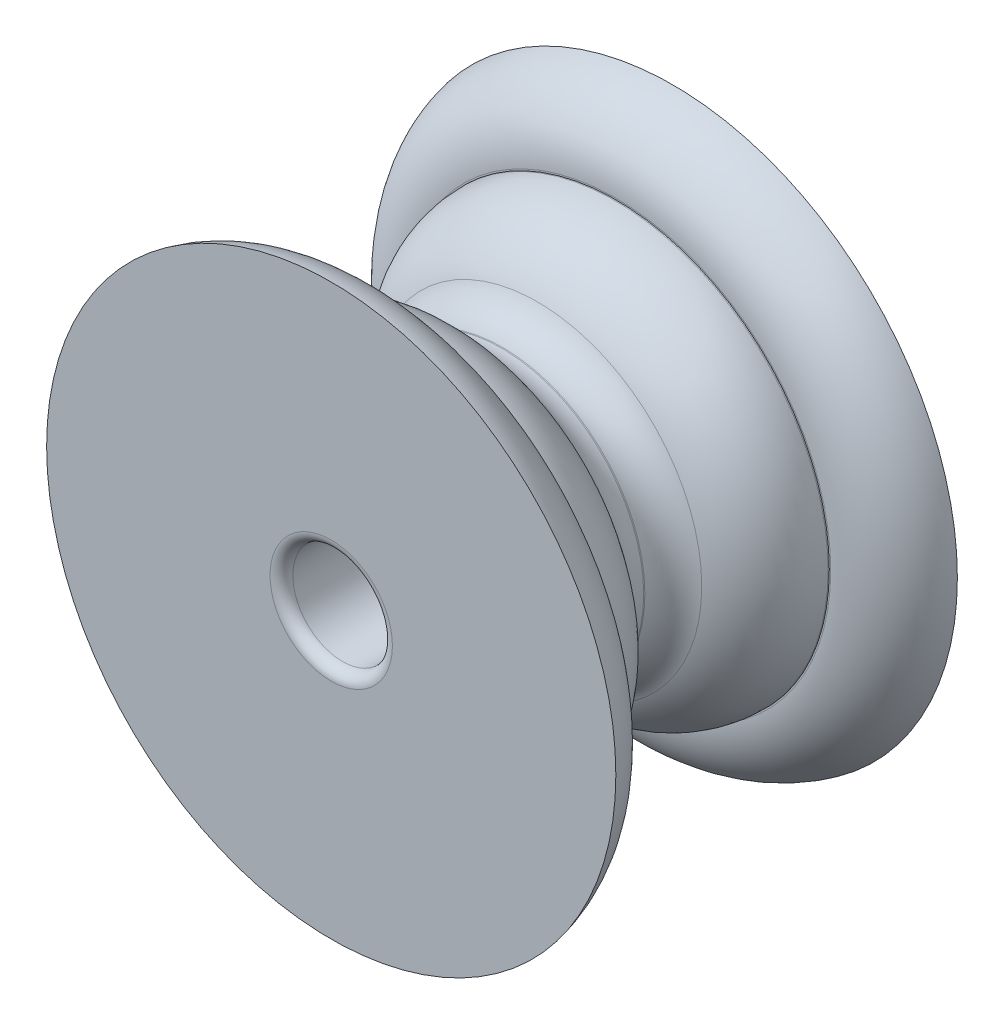
SolidWorks part; units mm, degrees
ref_plane "前视基准面" through (0, 0, 0) normal (0, 0, 1) x (1, 0, 0)
ref_plane "上视基准面" through (0, 0, 0) normal (0, 1, 0) x (1, 0, 0)
ref_plane "右视基准面" through (0, 0, 0) normal (1, 0, 0) x (0, 0, -1)
other "Configuration Table"
sketch "草图1" plane through (0, 0, 0) normal (0, 0, 1) x (1, 0, 0)
  circle A0 centre (0, 0) radius 10
  dimension "D1" = 20
extrude "凸台-拉伸1" add sketch "草图1" along normal blind 2
sketch "草图2" plane through (0, 0, 2) normal (0, 0, 1) x (1, 0, 0)
  circle A0 centre (0, 0) radius 7.5
  dimension "D1" = 15
extrude "凸台-拉伸2" add sketch "草图2" along normal blind 3
sketch "草图3" plane through (0, 0, 5) normal (0, 0, 1) x (1, 0, 0)
  circle A0 centre (0, 0) radius 5
  dimension "D1" = 10
extrude "凸台-拉伸3" add sketch "草图3" along normal blind 2
sketch "草图4" plane through (0, 0, 7) normal (0, 0, 1) x (1, 0, 0)
  circle A0 centre (0, 0) radius 7.5 construction
  circle A1 centre (0, 0) radius 7.5
extrude "凸台-拉伸4" add sketch "草图4" along normal blind 3
sketch "草图5" plane through (0, 0, 10) normal (0, 0, 1) x (1, 0, 0)
  circle A0 centre (0, 0) radius 10 construction
  circle A1 centre (0, 0) radius 10
extrude "凸台-拉伸5" add sketch "草图5" along normal blind 2
sketch "草图6" plane through (0, 0, 0) normal (0, 0, -1) x (-1, 0, 0)
  circle A0 centre (0, 0) radius 1.75
  dimension "D1" = 3.5
extrude "切除-拉伸1" cut sketch "草图6" against normal blind 22
fillet "圆角1" radius 3 2 edges at (7.5, 0, 5) (7.5, 0, 7)
fillet "圆角3" radius 1.35 2 edges at (5, 0, 5) (5, 0, 7)
fillet "圆角4" radius 0.4 2 edges at (1.75, 0, 12) (-1.75, 0, 0)
fillet "圆角5" radius 2.5 2 edges at (10, 0, 2) (10, 0, 10)
